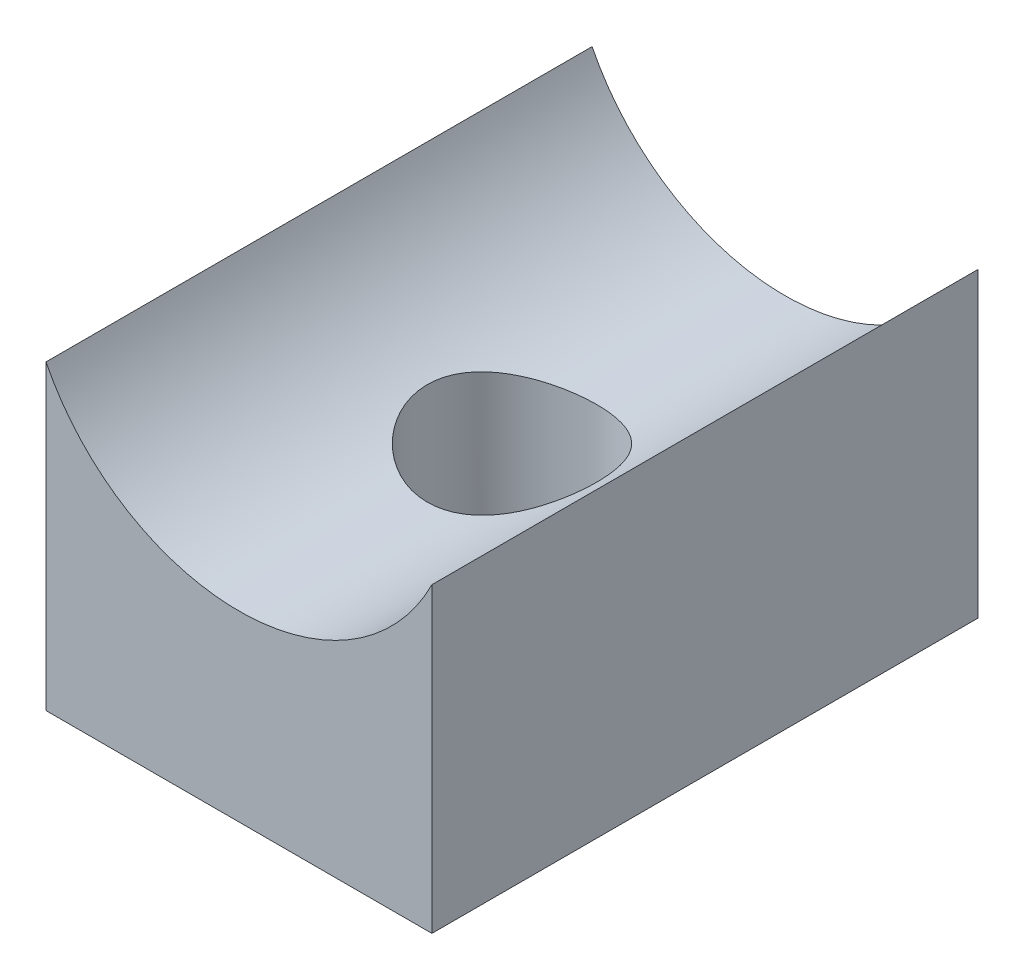
SolidWorks part; units mm, degrees
ref_plane "Front Plane" through (0, 0, 0) normal (0, 0, 1) x (1, 0, 0)
ref_plane "Top Plane" through (0, 0, 0) normal (0, 1, 0) x (1, 0, 0)
ref_plane "Right Plane" through (0, 0, 0) normal (1, 0, 0) x (0, 0, -1)
sketch "Sketch1" plane through (0, 0, 0) normal (0, 0, 1) x (1, 0, 0)
  line L0 (-3.5333, -5.53) -> (3.5333, -5.53)
  line L1 (3.5333, 0) -> (3.5333, -5.53)
  line L2 (-3.5333, 0) -> (-3.5333, -5.53)
  line L3 (55, 0) -> (-55, 0) construction
  line L4 (0, -44.7868) -> (0, 44.7868) construction
  arc A0 (-3.5333, 0) -> (3.5333, 0) centre (0, 1.7659) ccw
  point P2 (0, 0)
  point P3 (0, 0)
  point P10 (0, 0)
  point P11 (-14.5466, 0)
  point P12 (-15.9997, 0)
  point P13 (14.7596, 0)
  point P14 (0, 0)
  point P15 (0, 1.7659)
  dimension "D1" = 3.95
  dimension "D2" = 5.53
extrude "Boss-Extrude1" add sketch "Sketch1" along normal mid plane 10
sketch "Sketch2" plane through (0, -5.53, 0) normal (0, -1, 0) x (-1, 0, 0)
  circle A0 centre (0, 0) radius 1.55
  dimension "D1" = 3.1
extrude "Cut-Extrude1" cut sketch "Sketch2" against normal up to surface (3.3459 mm away) up to face at (0, -1.092, 0)
equation "\"tubeDiam\"=3.95"
equation "\"D1@Sketch1\"=\"tubeDiam\""
